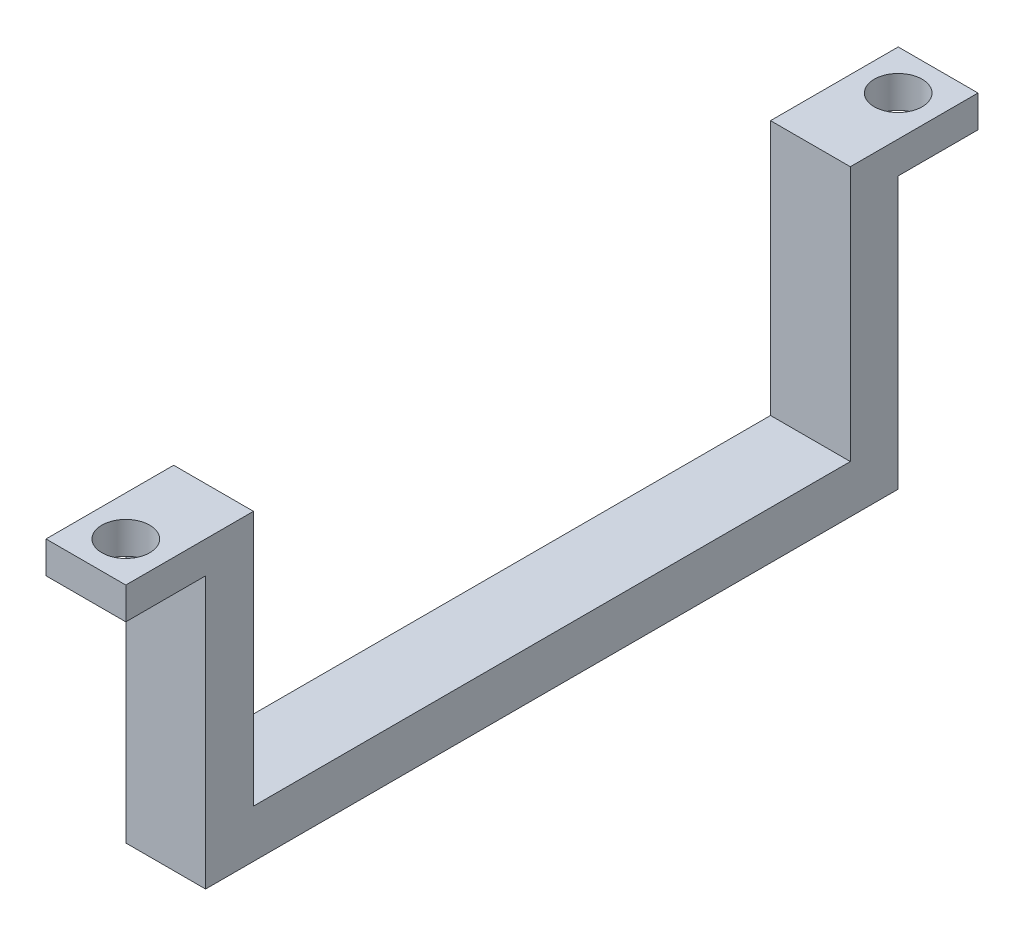
SolidWorks part; units mm, degrees
ref_plane "前视基准面" through (0, 0, 0) normal (0, 0, 1) x (1, 0, 0)
ref_plane "上视基准面" through (0, 0, 0) normal (0, 1, 0) x (1, 0, 0)
ref_plane "右视基准面" through (0, 0, 0) normal (1, 0, 0) x (0, 0, -1)
other "Configuration Table"
sketch "草图1" plane through (0, 0, 0) normal (0, 1, 0) x (1, 0, 0)
  line L5 (0, 0) -> (5, 0)
  line L6 (0, 0) -> (0, -8)
  line L7 (0, -8) -> (5, -8)
  line L8 (5, 0) -> (5, -8)
  line L9 (0, -53.4) -> (5, -53.4)
  line L10 (0, -53.4) -> (0, -45.4)
  line L11 (0, -45.4) -> (5, -45.4)
  line L12 (5, -53.4) -> (5, -45.4)
  line L13 (0, -8) -> (5, -8)
  line L14 (0, -8) -> (0, -5)
  line L15 (0, -5) -> (5, -5)
  line L16 (5, -8) -> (5, -5)
  line L17 (0, -45.4) -> (5, -45.4)
  line L18 (0, -45.4) -> (0, -48.4)
  line L19 (0, -48.4) -> (5, -48.4)
  line L20 (5, -45.4) -> (5, -48.4)
  circle A6 centre (2.5, -2.5) radius 1.5
  circle A10 centre (2.5, -50.9) radius 1.5
  dimension "D3" = 3
  dimension "D1" = 2.5
  dimension "D2" = 2.5
  dimension "D4" = 5
  dimension "D5" = 8
  dimension "D6" = 2.5
  dimension "D7" = 2.5
  dimension "D8" = 37.4
  dimension "D9" = 3
  dimension "D10" = 3
extrude "凸台-拉伸1" add sketch "草图1" along normal blind 2 contours L7 L8 L5 L6 | A10 | A6 | L12 L11 L10 L9
extrude "凸台-拉伸2" add sketch "草图1<6>" against normal blind 16 from surface contours L10 L19 L12 L11 | L15 L6 L7 L8 region at (2.5, 0, 6.5) region at (2.5, 0, 46.9) starting at face at (2.5, 2, 4)
sketch "草图1<6>" plane through (0, 0, 0) normal (0, 1, 0) x (1, 0, 0) same geometry as "草图1"
sketch "草图2" plane through (0, 0, 48.4) normal (0, 0, 1) x (1, 0, 0)
  line L0 (0, -14) -> (0, 0) construction
  line L1 (5, -14) -> (0, -14)
  line L2 (5, -14) -> (5, -17)
  line L3 (5, -17) -> (0, -17)
  line L4 (0, -14) -> (0, -17)
  dimension "D1" = 3
extrude "凸台-拉伸3" add sketch "草图2" against normal up to surface (43.4 mm away) up to face at (2.5, -7, 5)
